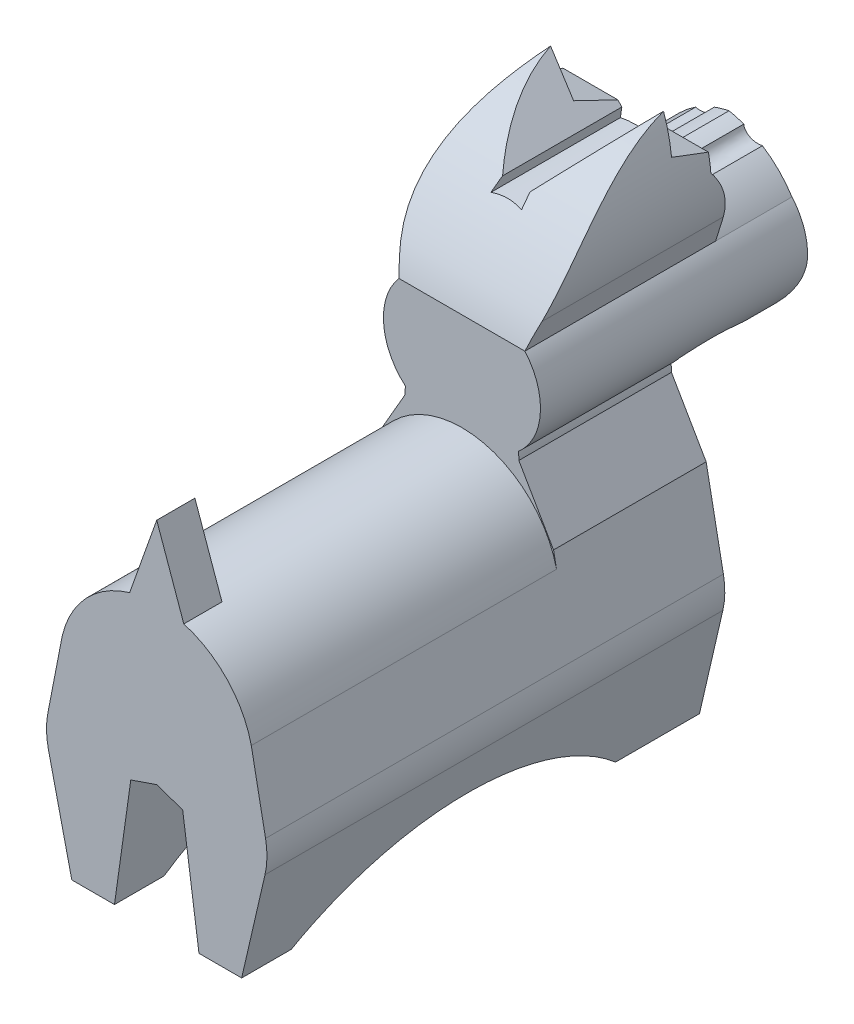
SolidWorks part; units mm, degrees
ref_plane "Front Plane" through (0, 0, 0) normal (0, 0, 1) x (1, 0, 0)
ref_plane "Top Plane" through (0, 0, 0) normal (0, 1, 0) x (1, 0, 0)
ref_plane "Right Plane" through (0, 0, 0) normal (1, 0, 0) x (0, 0, -1)
sketch "Sketch1" plane through (0, 0, 0) normal (0, 0, 1) x (1, 0, 0)
  line L0 (22.1, 52.9152) -> (22.1, 22.8983) construction
  line L1 (0, 0) -> (40, 0) construction
  line L2 (0, 0) -> (0, 60) construction
  line L3 (0, 60) -> (40, 60) construction
  line L4 (40, 0) -> (40, 60) construction
  line L5 (30.35, 42.7) -> (33.3943, 42.7) construction
  line L6 (100.8927, 244.9896) -> (530.8927, 244.9896) construction
  line L7 (31.356, 45.95) -> (32.2787, 45.95) construction
  line L8 (13.85, 42.7) -> (10.8057, 42.7) construction
  line L9 (12.844, 45.95) -> (11.9213, 45.95) construction
  line L10 (14.7, 60) -> (20.2893, 54)
  line L11 (24.1, 52.7) -> (23.9107, 54)
  line L12 (11.1727, 47.9417) -> (12.844, 45.95)
  line L13 (33.0273, 47.9417) -> (31.356, 45.95)
  line L14 (20.1, 52.7) -> (20.2893, 54)
  line L15 (13.85, 42.7) -> (12.844, 45.95)
  line L16 (29.5547, 29.8983) -> (34.1042, 22.0183)
  line L17 (34.1042, 22.0183) -> (36.7672, 8.3183)
  line L18 (30.35, 42.7) -> (31.356, 45.95)
  line L19 (29.5, 60) -> (23.9107, 54)
  line L20 (36.7672, 8.3183) -> (33.2303, -7.0017)
  line L21 (27.6373, -7.0017) -> (33.2303, -7.0017)
  line L22 (27.6373, -7.0017) -> (25.4995, 8.2095)
  line L23 (22.1, 22.8983) -> (22.1, 0) construction
  line L24 (25.4995, 8.2095) -> (22.1, 9.38)
  line L25 (29.5547, 29.8983) -> (31.8537, 29.8983) construction
  line L26 (34.1042, 22.0183) -> (35.3242, 22.0183) construction
  line L27 (36.7672, 8.3183) -> (37.3277, 8.3183) construction
  line L28 (25.4995, 8.2095) -> (24.459, 8.2095) construction
  line L29 (14.6453, 29.8983) -> (12.3463, 29.8983) construction
  line L30 (16.5627, -7.0017) -> (18.7005, 8.2095)
  line L31 (18.7005, 8.2095) -> (19.741, 8.2095) construction
  line L32 (18.7005, 8.2095) -> (22.1, 9.38)
  line L33 (7.4328, 8.3183) -> (6.8723, 8.3183) construction
  line L34 (10.0958, 22.0183) -> (8.8758, 22.0183) construction
  line L35 (10.0958, 22.0183) -> (7.4328, 8.3183)
  line L36 (16.5627, -7.0017) -> (10.9697, -7.0017)
  line L37 (7.4328, 8.3183) -> (10.9697, -7.0017)
  line L38 (14.6453, 29.8983) -> (10.0958, 22.0183)
  arc A0 (29.5, 60) -> (33.0273, 47.9417) centre (9.032, 47.4676) cw
  arc A1 (30.35, 42.7) -> (29.5, 30.8983) centre (24.0336, 37.2234) cw
  arc A2 (29.5, 30.8983) -> (22.1, 22.8983) centre (22.4356, 30.0103) cw
  arc A3 (14.7, 30.8983) -> (22.1, 22.8983) centre (21.7644, 30.0103) ccw
  arc A4 (20.1, 52.7) -> (24.1, 52.7) centre (22.1, 43.5152) cw
  arc A5 (14.7, 60) -> (11.1727, 47.9417) centre (35.168, 47.4676) ccw
  arc A6 (13.85, 42.7) -> (14.7, 30.8983) centre (20.1664, 37.2234) ccw
  dimension "D5" = 24
  dimension "D6" = 8.36
  dimension "D7" = 7.12
  dimension "D11" = 2.6
  dimension "D15" = 8
  dimension "D19" = 9.4
  dimension "D3" = 4
  dimension "D1" = 60
  dimension "D2" = 40
  dimension "D4" = 8.2
  dimension "D8" = 72.8
  dimension "D9" = 50
  dimension "D10" = 10.5
  dimension "D12" = 3.25
  dimension "D13" = 9.65
  dimension "D14" = 17.3
  dimension "D16" = 17.9
  dimension "D17" = 1.3
  dimension "D18" = 7.3
  dimension "D20" = 60
  dimension "D21" = 79
  dimension "D22" = 103
  dimension "D23" = 15.32
  dimension "D24" = 13.7
  dimension "D25" = 7.88
  dimension "D26" = 1
  dimension "D27" = 98
  dimension "D28" = 161
  dimension "D29" = 9.38
extrude "Boss-Extrude1" add sketch "Sketch1" along normal blind 60 contours L15 A6 A3 A2 A1 L18 L13 A0 L19 L11 A4 L14 L10 A5 L12 | A3 L38 L35 L37 L36 L30 L32 L24 L22 L21 L20 L17 L16 A2 region at (22.1, 41.2894, 0) region at (22.1, 10.8949, 0)
sketch "Sketch2" plane through (0, 0, 60) normal (0, 0, 1) x (1, 0, 0)
  line L0 (10.0958, 22.0183) -> (7.4328, 8.3183) construction
  line L1 (34.1042, 22.0183) -> (36.7672, 8.3183) construction
  line L2 (29.5547, 29.8983) -> (14.6453, 29.8983) construction
  line L3 (9.707, 20.0183) -> (10.0958, 22.0183)
  line L4 (10.0958, 22.0183) -> (14.6453, 29.8983)
  line L6 (13.85, 42.7) -> (12.844, 45.95)
  line L7 (12.844, 45.95) -> (11.1727, 47.9417)
  line L8 (14.7, 60) -> (20.2893, 54)
  line L9 (20.2893, 54) -> (20.1, 52.7)
  line L10 (24.1, 52.7) -> (23.9107, 54)
  line L11 (23.9107, 54) -> (29.5, 60)
  line L12 (33.0273, 47.9417) -> (31.356, 45.95)
  line L13 (31.356, 45.95) -> (30.35, 42.7)
  line L15 (29.5547, 29.8983) -> (34.1042, 22.0183)
  line L16 (34.1042, 22.0183) -> (34.493, 20.0183)
  arc A0 (9.707, 20.0183) -> (34.493, 20.0183) centre (22.1, 17.1857) cw
  arc A1 (14.7, 30.8983) -> (22.1, 22.8983) centre (21.7644, 30.0103) ccw construction
  arc A2 (14.7, 30.8983) -> (13.85, 42.7) centre (20.1664, 37.2234) cw
  arc A3 (20.1, 52.7) -> (24.1, 52.7) centre (22.1, 43.5152) cw
  arc A4 (14.7, 60) -> (11.1727, 47.9417) centre (35.168, 47.4676) ccw
  arc A5 (29.5, 60) -> (33.0273, 47.9417) centre (9.032, 47.4676) cw
  arc A6 (14.7, 60) -> (11.1727, 47.9417) centre (35.168, 47.4676) ccw construction
  arc A7 (33.0273, 47.9417) -> (29.5, 60) centre (9.032, 47.4676) ccw construction
  arc A8 (30.35, 42.7) -> (29.5, 30.8983) centre (24.0336, 37.2234) cw
  arc A9 (29.5, 30.8983) -> (30.35, 42.7) centre (24.0336, 37.2234) ccw construction
  arc A10 (14.7, 30.8983) -> (14.6453, 29.8983) centre (21.7644, 30.0103) ccw
  arc A11 (29.5, 30.8983) -> (29.5547, 29.8983) centre (22.4356, 30.0103) cw
  arc A12 (22.1, 22.8983) -> (29.5, 30.8983) centre (22.4356, 30.0103) ccw construction
  point P3 (22.1, 29.8983)
  dimension "D1" = 2
extrude "Cut-Extrude1" cut sketch "Sketch2" against normal blind 40
extrude "Boss-Extrude2" add sketch "Sketch1<4>" against normal blind 15 contours L15 A6 A3 A2 A1 L18 L13 A0 L19 L11 A4 L14 L10 A5 L12 region at (22.1, 41.2894, 0)
sketch "Sketch1<4>" plane through (0, 0, 0) normal (0, 0, 1) x (1, 0, 0) same geometry as "Sketch1"
sketch "Sketch4" plane through (0, 0, 0) normal (1, 0, 0) x (0, 0, -1)
  line L0 (-0.9847, 60) -> (-1.69, 56)
  line L1 (0, 22.0183) -> (0, 32.0983)
  line L2 (-1.69, 56) -> (2.76, 54.5541)
  line L3 (2.76, 54.5541) -> (2.76, 52.3341)
  line L4 (2.76, 52.3341) -> (15, 48.3571)
  line L5 (0, 42.7) -> (0, 30.8983) construction
  line L6 (15, 30.8983) -> (15, 42.7) construction
  line L7 (-20, 30.8983) -> (15, 30.8983) construction
  line L9 (15, 22.8903) -> (15, 30.8983) construction
  line L10 (15, 33.7783) -> (12.1, 29.3983)
  line L11 (-7.9686, 55) -> (1.3877, 55) construction
  line L12 (-0.9847, 60) -> (-7.9686, 55)
  line L13 (-7.9686, 55) -> (-20, 29.8983)
  line L15 (-20, 45.95) -> (15, 45.95) construction
  line L16 (0, 22.0183) -> (15, 22.0183)
  line L17 (2.76, 52.3341) -> (15, 52.3341) construction
  line L18 (15, 22.0183) -> (15, 60)
  line L19 (15, 60) -> (-20, 60)
  line L20 (-20, 60) -> (-20, 29.8983)
  line L21 (-20, 60) -> (15, 60) construction
  arc A0 (12.1, 29.3983) -> (0, 32.0983) centre (3.696, 20.1991) ccw
  dimension "D2" = 12.46
  dimension "D1" = 5
  dimension "D3" = 80
  dimension "D4" = 18
  dimension "D5" = 12.24
  dimension "D6" = 2.22
  dimension "D7" = 4
  dimension "D8" = 4.45
  dimension "D9" = 35.6
  dimension "D10" = 4.38
  dimension "D11" = 1.2
  dimension "D12" = 2.7
  dimension "D15" = 2.9
extrude "Cut-Extrude5" cut sketch "Sketch4" against normal through all both and the other way through all contours L19 L20 L13 L12 L0 L2 L3 L4 L18 | L10 L16 L18 region at (0, 55.4518, -8.0905) region at (0, 26.9744, -7.2745)
sketch "Sketch8" plane through (0, 0, -15) normal (0, 0, -1) x (-1, 0, 0)
  line L0 (-33.0155, 48.3571) -> (-11.1845, 48.3571) construction
  line L1 (-22.1, 52.9152) -> (-22.1, 33.7783) construction
  line L2 (-31.6507, 33.7783) -> (-12.5493, 33.7783) construction
  line L3 (-30.35, 42.7) -> (-36.35, 42.7)
  line L4 (-36.35, 42.7) -> (-36.35, 52.9152)
  line L5 (-36.35, 52.9152) -> (-7.85, 52.9152)
  line L6 (-7.85, 52.9152) -> (-7.85, 42.7)
  line L7 (-7.85, 42.7) -> (-13.85, 42.7)
  arc A0 (-30.35, 42.7) -> (-22.1, 48.3571) centre (-19.5618, 35.8113) cw
  arc A1 (-20.1, 52.7) -> (-24.1, 52.7) centre (-22.1, 43.5152) ccw construction
  arc A2 (-13.85, 42.7) -> (-22.1, 48.3571) centre (-24.6382, 35.8113) ccw
  dimension "D1" = 12.8
  dimension "D2" = 6
  dimension "D3" = 6
extrude "Cut-Extrude6" cut sketch "Sketch8" against normal blind 10
fillet "Fillet2" radius 10 1 edges at (22.1, 33.7783, -15)
fillet "Fillet3" radius 10 1 edges at (22.1, 51.6063, -5)
sketch "Sketch9" plane through (0, 0, 0) normal (1, 0, 0) x (0, 0, -1)
  line L0 (-60, -7.0017) -> (0, -7.0017) construction
  line L1 (-60, 8.3183) -> (-60, -7.0017) construction
  line L2 (0, 8.3183) -> (0, -7.0017) construction
  line L3 (-20, 42.7) -> (-20, 60)
  line L4 (-20, 60) -> (-0.9847, 60)
  line L5 (-11, -7.0017) -> (-53.5, -7.0017)
  arc A0 (-53.5, -7.0017) -> (-11, -7.0017) centre (-32.25, -30.9274) cw
  arc A1 (-0.9847, 60) -> (-20, 42.7) centre (3.9376, 35.4894) ccw
  dimension "D1" = 32
  dimension "D4" = 25
  dimension "D2" = 6.5
  dimension "D3" = 11
extrude "Cut-Extrude8" cut sketch "Sketch9" along normal through all both and the other way through all
sketch "Sketch10" plane through (0, 0, 60) normal (0, 0, 1) x (1, 0, 0)
  line L0 (18.55, 29.3925) -> (22.1, 39.3925)
  line L1 (22.1, 52.9152) -> (22.1, 22.8983) construction
  line L2 (22.1, 39.3925) -> (25.65, 29.3925)
  line L8 (30.35, 42.7) -> (13.85, 42.7)
  line L9 (14.6453, 29.8983) -> (10.0958, 22.0183)
  line L10 (10.0958, 22.0183) -> (9.707, 20.0183)
  line L11 (34.493, 20.0183) -> (34.1042, 22.0183)
  line L12 (34.1042, 22.0183) -> (29.5547, 29.8983)
  arc A0 (34.493, 20.0183) -> (9.707, 20.0183) centre (22.1, 17.1857) ccw construction
  arc A6 (13.85, 42.7) -> (14.7, 30.8983) centre (20.1664, 37.2234) ccw
  arc A7 (14.7, 30.8983) -> (14.6453, 29.8983) centre (21.7644, 30.0103) ccw
  arc A8 (34.493, 20.0183) -> (9.707, 20.0183) centre (22.1, 17.1857) ccw
  arc A9 (29.5547, 29.8983) -> (29.5, 30.8983) centre (22.4356, 30.0103) ccw
  arc A10 (29.5, 30.8983) -> (30.35, 42.7) centre (24.0336, 37.2234) ccw
  arc A13 (25.65, 29.3925) -> (18.55, 29.3925) centre (22.1, 17.1857) ccw
  dimension "D1" = 10
  dimension "D2" = 3.55
  dimension "D3" = 3.55
  dimension "D4" = 0
extrude "Boss-Extrude3" add sketch "Sketch10" against normal blind 5
fillet "Fillet4" radius 10 1 edges at (36.7672, 8.3183, 30)
fillet "Fillet5" radius 10 1 edges at (7.4328, 8.3183, 30)
sketch "Sketch11" plane through (0, 0, -15) normal (0, 0, -1) x (-1, 0, 0)
  line L0 (-20.1727, 47.8071) -> (-15.291, 47.8071) construction
  line L1 (-22.1, 48.3571) -> (-22.1, 36.7887) construction
  line L2 (-32.3823, 36.7887) -> (-11.8177, 36.7887) construction
  arc A0 (-16.9257, 46.0268) -> (-22.1, 48.3571) centre (-24.6382, 35.8113) ccw construction
  ellipse E0 centre (-18.1843, 48.0221) end of major axis (-16.1959, 48.2371) minor radius 1.5
  ellipse E1 centre (-26.0157, 48.0221) end of major axis (-28.0041, 48.2371) minor radius 1.5
  dimension "D1" = 2
  dimension "D2" = 1.5
  dimension "D3" = 9
  dimension "D4" = 0.43
extrude "Cut-Extrude9" cut sketch "Sketch11" against normal blind 12
sketch "Sketch13" plane through (0, 0, -15) normal (0, 0, -1) x (-1, 0, 0)
  line L0 (-29.5292, 29.3983) -> (-14.6708, 29.3983) construction
  line L2 (-22.1, 48.4016) -> (-22.1, 29.4279) construction
  line L3 (-22.1, 52.9152) -> (-22.1, 22.8983) construction
  line L4 (-29.5, 30.8983) -> (-30.5, 30.8983)
  line L5 (-30.5, 30.8983) -> (-30.5, 29.3983)
  line L6 (-14.6708, 29.3983) -> (-29.5292, 29.3983)
  line L7 (-30.5, 29.3983) -> (-29.5292, 29.3983)
  line L8 (-14.7, 30.8983) -> (-13.7, 30.8983)
  line L9 (-13.7, 30.8983) -> (-13.7, 29.3983)
  line L10 (-13.7, 29.3983) -> (-14.6708, 29.3983)
  arc A0 (-29.5, 30.8983) -> (-14.7, 30.8983) centre (-22.1, 48.4016) ccw
  arc A1 (-22.1, 22.8983) -> (-14.7, 30.8983) centre (-21.7644, 30.0103) ccw construction
  dimension "D1" = 1
  dimension "D2" = 1
extrude "Cut-Extrude10" cut sketch "Sketch13" against normal blind 12 contours A0 L6 | A0 L6 region at (28.3464, 29.9335, -15) region at (15.8536, 29.9335, -15)
sketch "Sketch14" plane through (0, 0, -15) normal (0, 0, -1) x (-1, 0, 0)
  line L0 (-22.1, 52.9152) -> (-22.1, 36.7676) construction
  line L1 (-22.1, 52.9152) -> (-22.1, 22.8983) construction
  line L2 (-14.7, 60) -> (-10.7, 60)
  line L3 (0, 60) -> (-40, 60) construction
  line L4 (-10.7, 60) -> (-10.7, 45.95)
  line L5 (-10.7, 45.95) -> (-12.844, 45.95)
  line L6 (-29.5, 60) -> (-33.5, 60)
  line L7 (-33.5, 60) -> (-33.5, 45.95)
  line L8 (-33.5, 45.95) -> (-31.356, 45.95)
  arc A0 (-14.7, 60) -> (-12.844, 45.95) centre (-30.176, 50.808) cw
  arc A3 (-29.5, 60) -> (-31.356, 45.95) centre (-14.024, 50.808) ccw
  dimension "D1" = 18
  dimension "D2" = 4
  dimension "D3" = 4
extrude "Cut-Extrude12" cut sketch "Sketch14" against normal through all
sketch "Sketch16" plane through (0, 3.39, 5.1201) normal (0, -0.5521, -0.8338) x (-1, 0, 0)
  line L1 (-14.2992, 33.4349) -> (-29.9008, 33.4349) construction
  line L2 (-22.1, 44.1209) -> (-22.1, 19.0926) construction
  arc A0 (-29.6355, 33.1349) -> (-22.1, 34.7349) centre (-27.0818, 39.6524) ccw
  arc A1 (-22.1, 34.7349) -> (-14.5645, 33.1349) centre (-17.1182, 39.6524) ccw
  arc A2 (-29.6355, 33.1349) -> (-22.1, 35.3349) centre (-27.4921, 39.7986) ccw
  arc A3 (-22.1, 35.3349) -> (-14.5645, 33.1349) centre (-16.7079, 39.7986) ccw
  ellipse E1 centre (-20.1664, 40.5772) end of major axis (-20.1664, 30.5509) minor radius 8.36 (-14.7, 32.9913) -> (-14.2992, 33.4349) ccw construction
  ellipse E2 centre (-24.0336, 40.5772) end of major axis (-24.0336, 50.6036) minor radius 8.36 (-29.9008, 33.4349) -> (-29.5, 32.9913) ccw construction
  dimension "D3" = 7
  dimension "D4" = 7
  dimension "D6" = 7
  dimension "D8" = 7
  dimension "D1" = 0.3
  dimension "D2" = 0.3
  dimension "D5" = 1.3
  dimension "D7" = 0.6
extrude "Cut-Extrude17" cut sketch "Sketch16" against normal blind 1
scale "Scale1" scale about centroid uniform scaling yes scale factor 0.5
